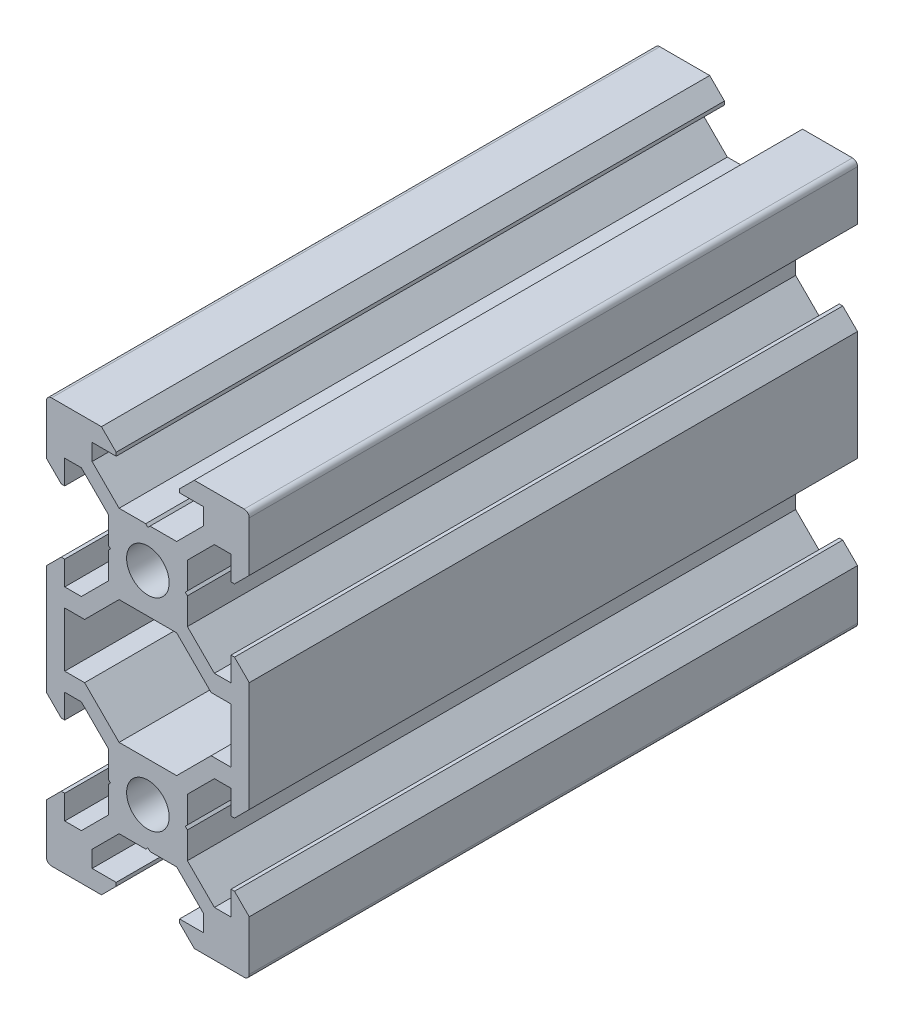
SolidWorks part; units mm, degrees
material "6061-T6 (SS)"
ref_plane "Front Plane" through (0, 0, 0) normal (0, 0, 1) x (1, 0, 0)
ref_plane "Top Plane" through (0, 0, 0) normal (0, 1, 0) x (1, 0, 0)
ref_plane "Right Plane" through (0, 0, 0) normal (1, 0, 0) x (0, 0, -1)
sketch "Sketch1" plane through (0, 0, 0) normal (0, 0, 1) x (1, 0, 0)
  line L0 (0, 0) -> (10, 0) construction
  line L1 (9.5, -20) -> (-9.5, -20)
  line L2 (10, -19.5) -> (10, 19.5)
  line L3 (9.5, 20) -> (-9.5, 20)
  line L4 (-10, -19.5) -> (-10, 19.5)
  line L5 (10, -20) -> (-10, 20) construction
  line L6 (10, 20) -> (-10, -20) construction
  circle A0 centre (0, 10) radius 2.1
  circle A1 centre (0, -10) radius 2.1
  arc A2 (-9.5, -20) -> (-10, -19.5) centre (-9.5, -19.5) cw
  arc A3 (9.5, -20) -> (10, -19.5) centre (9.5, -19.5) ccw
  arc A4 (10, 19.5) -> (9.5, 20) centre (9.5, 19.5) ccw
  arc A5 (-9.5, 20) -> (-10, 19.5) centre (-9.5, 19.5) ccw
  point P0 (0, 0)
  line B0 (0, 10) -> (0, 20) construction
  line B1 (0, 13.69) -> (-0.21, 13.9)
  line B2 (-0.21, 13.9) -> (-2.8393, 13.9)
  line B3 (-2.8393, 13.9) -> (-5.5, 16.5607)
  line B4 (-5.5, 16.5607) -> (-5.5, 18.2)
  line B5 (-5.5, 18.2) -> (-3.125, 18.2)
  line B6 (-3.125, 18.2) -> (-3.125, 18.545)
  line B7 (-3.125, 18.545) -> (-4.58, 20)
  line B8 (-4.58, 20) -> (4.58, 20)
  line B9 (0, 10) -> (-5.9132, 15.9132) construction
  line B10 (3.125, 18.545) -> (4.58, 20)
  line B11 (3.125, 18.2) -> (3.125, 18.545)
  line B12 (5.5, 18.2) -> (3.125, 18.2)
  line B13 (5.5, 16.5607) -> (5.5, 18.2)
  line B14 (2.8393, 13.9) -> (5.5, 16.5607)
  line B15 (0.21, 13.9) -> (2.8393, 13.9)
  line B16 (0, 13.69) -> (0.21, 13.9)
  line B17 (0, 10) -> (-10, 10) construction
  line B18 (-3.69, 10) -> (-3.9, 9.79)
  line B19 (-3.9, 9.79) -> (-3.9, 7.1607)
  line B20 (-3.9, 7.1607) -> (-6.5607, 4.5)
  line B21 (-6.5607, 4.5) -> (-8.2, 4.5)
  line B22 (-8.2, 4.5) -> (-8.2, 6.875)
  line B23 (-8.2, 6.875) -> (-8.545, 6.875)
  line B24 (-8.545, 6.875) -> (-10, 5.42)
  line B25 (-10, 5.42) -> (-10, 14.58)
  line B26 (0, 10) -> (-5.9132, 4.0868) construction
  line B27 (-8.545, 13.125) -> (-10, 14.58)
  line B28 (-8.2, 13.125) -> (-8.545, 13.125)
  line B29 (-8.2, 15.5) -> (-8.2, 13.125)
  line B30 (-6.5607, 15.5) -> (-8.2, 15.5)
  line B31 (-3.9, 12.8393) -> (-6.5607, 15.5)
  line B32 (-3.9, 10.21) -> (-3.9, 12.8393)
  line B33 (-3.69, 10) -> (-3.9, 10.21)
  line B34 (0, -10) -> (-10, -10) construction
  line B35 (-3.69, -10) -> (-3.9, -10.21)
  line B36 (-3.9, -10.21) -> (-3.9, -12.8393)
  line B37 (-3.9, -12.8393) -> (-6.5607, -15.5)
  line B38 (-6.5607, -15.5) -> (-8.2, -15.5)
  line B39 (-8.2, -15.5) -> (-8.2, -13.125)
  line B40 (-8.2, -13.125) -> (-8.545, -13.125)
  line B41 (-8.545, -13.125) -> (-10, -14.58)
  line B42 (-10, -14.58) -> (-10, -5.42)
  line B43 (0, -10) -> (-5.9132, -15.9132) construction
  line B44 (-8.545, -6.875) -> (-10, -5.42)
  line B45 (-8.2, -6.875) -> (-8.545, -6.875)
  line B46 (-8.2, -4.5) -> (-8.2, -6.875)
  line B47 (-6.5607, -4.5) -> (-8.2, -4.5)
  line B48 (-3.9, -7.1607) -> (-6.5607, -4.5)
  line B49 (-3.9, -9.79) -> (-3.9, -7.1607)
  line B50 (-3.69, -10) -> (-3.9, -9.79)
  line B51 (0, -10) -> (0, -20) construction
  line B52 (0, -13.69) -> (0.21, -13.9)
  line B53 (0.21, -13.9) -> (2.8393, -13.9)
  line B54 (2.8393, -13.9) -> (5.5, -16.5607)
  line B55 (5.5, -16.5607) -> (5.5, -18.2)
  line B56 (5.5, -18.2) -> (3.125, -18.2)
  line B57 (3.125, -18.2) -> (3.125, -18.545)
  line B58 (3.125, -18.545) -> (4.58, -20)
  line B59 (4.58, -20) -> (-4.58, -20)
  line B60 (0, -10) -> (5.9132, -15.9132) construction
  line B61 (-3.125, -18.545) -> (-4.58, -20)
  line B62 (-3.125, -18.2) -> (-3.125, -18.545)
  line B63 (-5.5, -18.2) -> (-3.125, -18.2)
  line B64 (-5.5, -16.5607) -> (-5.5, -18.2)
  line B65 (-2.8393, -13.9) -> (-5.5, -16.5607)
  line B66 (-0.21, -13.9) -> (-2.8393, -13.9)
  line B67 (0, -13.69) -> (-0.21, -13.9)
  line B68 (0, -10) -> (10, -10) construction
  line B69 (3.69, -10) -> (3.9, -9.79)
  line B70 (3.9, -9.79) -> (3.9, -7.1607)
  line B71 (3.9, -7.1607) -> (6.5607, -4.5)
  line B72 (6.5607, -4.5) -> (8.2, -4.5)
  line B73 (8.2, -4.5) -> (8.2, -6.875)
  line B74 (8.2, -6.875) -> (8.545, -6.875)
  line B75 (8.545, -6.875) -> (10, -5.42)
  line B76 (10, -5.42) -> (10, -14.58)
  line B77 (0, -10) -> (5.9132, -4.0868) construction
  line B78 (8.545, -13.125) -> (10, -14.58)
  line B79 (8.2, -13.125) -> (8.545, -13.125)
  line B80 (8.2, -15.5) -> (8.2, -13.125)
  line B81 (6.5607, -15.5) -> (8.2, -15.5)
  line B82 (3.9, -12.8393) -> (6.5607, -15.5)
  line B83 (3.9, -10.21) -> (3.9, -12.8393)
  line B84 (3.69, -10) -> (3.9, -10.21)
  line B85 (0, 10) -> (10, 10) construction
  line B86 (3.69, 10) -> (3.9, 10.21)
  line B87 (3.9, 10.21) -> (3.9, 12.8393)
  line B88 (3.9, 12.8393) -> (6.5607, 15.5)
  line B89 (6.5607, 15.5) -> (8.2, 15.5)
  line B90 (8.2, 15.5) -> (8.2, 13.125)
  line B91 (8.2, 13.125) -> (8.545, 13.125)
  line B92 (8.545, 13.125) -> (10, 14.58)
  line B93 (10, 14.58) -> (10, 5.42)
  line B94 (0, 10) -> (5.9132, 15.9132) construction
  line B95 (8.545, 6.875) -> (10, 5.42)
  line B96 (8.2, 6.875) -> (8.545, 6.875)
  line B97 (8.2, 4.5) -> (8.2, 6.875)
  line B98 (6.5607, 4.5) -> (8.2, 4.5)
  line B99 (3.9, 7.1607) -> (6.5607, 4.5)
  line B100 (3.9, 9.79) -> (3.9, 7.1607)
  line B101 (3.69, 10) -> (3.9, 9.79)
  line B102 (-8.2, -2.7) -> (-8.2, 2.7)
  line B103 (-8.2, 2.7) -> (-6.2393, 2.7)
  line B104 (-6.2393, 2.7) -> (-2.8393, 6.1)
  line B105 (-2.8393, 6.1) -> (2.8393, 6.1)
  line B106 (0, 6.1) -> (0, 0) construction
  line B107 (0, 0) -> (-8.2, 0) construction
  line B108 (6.2393, 2.7) -> (2.8393, 6.1)
  line B109 (8.2, 2.7) -> (6.2393, 2.7)
  line B110 (8.2, -2.7) -> (8.2, 2.7)
  line B111 (8.2, -2.7) -> (6.2393, -2.7)
  line B112 (6.2393, -2.7) -> (2.8393, -6.1)
  line B113 (-2.8393, -6.1) -> (2.8393, -6.1)
  line B114 (-6.2393, -2.7) -> (-2.8393, -6.1)
  line B115 (-8.2, -2.7) -> (-6.2393, -2.7)
  line B116 (0, 6.1) -> (0, 10) construction
  line B117 (0, 10) -> (-5.0927, 4.9073) construction
  dimension "D4" = 4.2
  dimension "D5" = 0.5
  dimension "D1" = 20
  dimension "D2" = 40
  dimension "D3" = 20
sketch_block_instance "V Slot 1-4"
sketch_block "V Slot 1" parameters "D1"=10, "D2"=11, "D3"=4.3, "D4"=1.8, "D5"=0.21, "D6"=45, "D7"=9.16, "D8"=1.5, "D9"=6.25
sketch_block_instance "V Slot 1-5"
sketch_block_instance "V Slot 1-6"
sketch_block_instance "V Slot 1-7"
sketch_block_instance "V Slot 1-8"
sketch_block_instance "V Slot 1-9"
sketch_block_instance "Center Cutout 1-1"
sketch_block "Center Cutout 1" parameters "D1"=5.4, "D2"=12.2, "D3"=8.2, "D4"=45, "D5"=10, "D6"=1.5
extrude "Boss-Extrude1" add sketch "Sketch1" along normal blind 60 contours B101 B86 B87 B88 B89 B90 B91 B92 L2 A4 L3 B10 B11 B12 B13 B14 B15 B16 B1 B2 B3 B4 B5 B6 B7 A5 L4 B27 B28 B29 B30 B31 B32 B33 B18 B19 B20 B21 B22 B23 B24 B44 B45 B46 B47 B48 B49 B50 B35 region at (7.04, -19.5528, 0)
